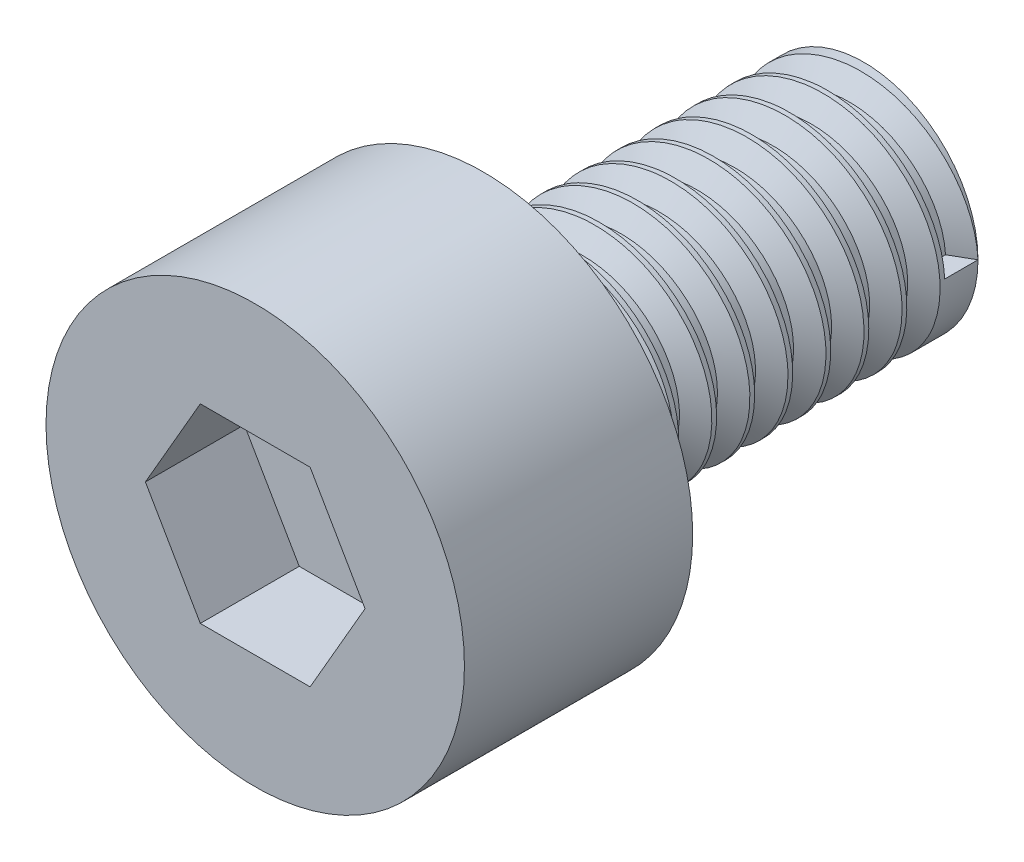
SolidWorks part; units mm, degrees
ref_plane "Front Plane" through (0, 0, 0) normal (0, 0, 1) x (1, 0, 0)
ref_plane "Top Plane" through (0, 0, 0) normal (0, 1, 0) x (1, 0, 0)
ref_plane "Right Plane" through (0, 0, 0) normal (1, 0, 0) x (0, 0, -1)
sketch "Sketch1" plane through (0, 0, 0) normal (0, 0, 1) x (1, 0, 0)
  circle A0 centre (0, 0) radius 1.5
  dimension "D1" = 3
extrude "Boss-Extrude1" add sketch "Sketch1" against normal blind 5
sketch "Sketch2" plane through (0, 0, 0) normal (0, 0, 1) x (1, 0, 0)
  circle A0 centre (0, 0) radius 2.75
  dimension "D1" = 5.5
extrude "Boss-Extrude2" add sketch "Sketch2" along normal blind 3
ref_plane "Mat_dau_vit" through (0, 0, 3) normal (0, 0, 1) x (1, 0, 0)
sketch "Sketch3" plane through (0, 0, 3) normal (0, 0, 1) x (1, 0, 0)
  line L1 (1.4434, 0) -> (0.7217, 1.25)
  line L2 (0.7217, 1.25) -> (-0.7217, 1.25)
  line L3 (-0.7217, 1.25) -> (-1.4434, 0)
  line L4 (-1.4434, 0) -> (-0.7217, -1.25)
  line L5 (-0.7217, -1.25) -> (0.7217, -1.25)
  line L6 (0.7217, -1.25) -> (1.4434, 0)
  circle A0 centre (0, 0) radius 1.25 construction
  dimension "D1" = 2.5
extrude "Cut-Extrude1" cut sketch "Sketch3" against normal blind 1.3
thread "Ren_ngoai_M3x0_5" pitch 0.5 method cut profile "Thread Profile1" start angle 0, offset 0, length 0, pitch 0.5, diameter 3
ref_plane "Plane2" through (1.5, 0, -5) normal (0, -1, 0) x (1, 0, 0)
sketch "Thread Profile1" plane through (1.5, 0, -5) normal (0, -1, 0) x (1, 0, 0)
  line L0 (0, 0) -> (0, 0.5) construction
  line L11 (0, 0) -> (0, 0.4375)
  line L12 (0, 0.4375) -> (-0.2706, 0.2812)
  line L13 (-0.2706, 0.2812) -> (-0.2706, 0.1562)
  line L15 (-0.2706, 0.1562) -> (0, 0)
  line L17 (-0.2706, 0.2187) -> (0, 0.2187) construction
  point P2 (0, 0)
  dimension "Pitch" = 0.5
  dimension "Profile_Angle" = 60
  dimension "Profile_Land" = 0.125
  dimension "Profile_Height" = 0.2706
